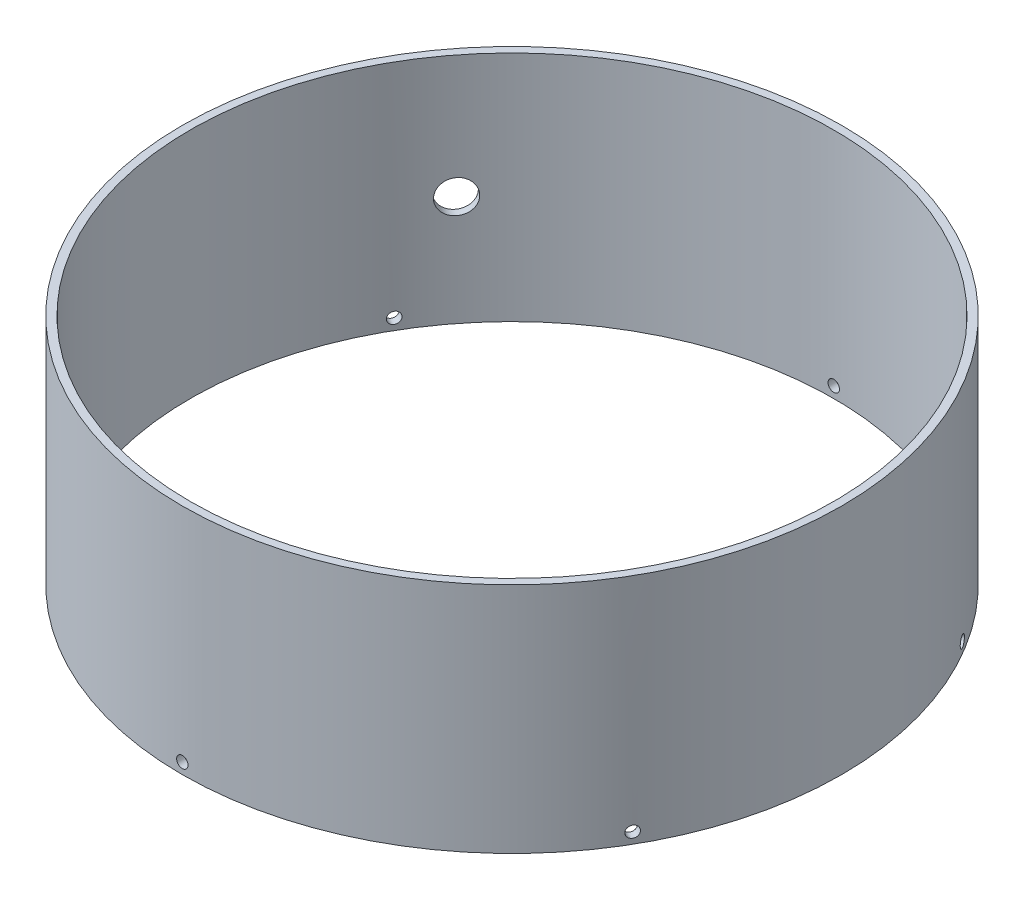
SolidWorks part; units mm, degrees
material "E-Glass Fiber"
ref_plane "Front Plane" through (0, 0, 0) normal (0, 0, 1) x (1, 0, 0)
ref_plane "Top Plane" through (0, 0, 0) normal (0, 1, 0) x (1, 0, 0)
ref_plane "Right Plane" through (0, 0, 0) normal (1, 0, 0) x (0, 0, -1)
sketch "Sketch2" plane through (0, 0, 0) normal (0, 1, 0) x (1, 0, 0)
  circle A0 centre (0, 0) radius 76.2
  circle A1 centre (0, 0) radius 74.3712
  dimension "D1" = 152.4
  dimension "D2" = 1.8288
extrude "Boss-Extrude1" add sketch "Sketch2" along normal blind 53.7718 contours A0 A1 region at (-75.9845, 0, 0)
sketch "Sketch3" plane through (0, 0, 0) normal (0, 0, 1) x (1, 0, 0)
  circle A0 centre (0, 2.54) radius 1.3208
  dimension "D1" = 2.6416
  dimension "D2" = 2.54
extrude "Cut-Extrude1" cut sketch "Sketch3" along normal up to surface (76.1886 mm away) contours A0 region at (0, 2.54, 0) up to face at (0, 53.7718, 76.2)
pattern_circular "CirPattern1" count 6 over 360 about axis through (0, 53.7718, 0) along (0, -1, 0) of "Cut-Extrude1"
sketch "Sketch4" plane through (0, 0, 0) normal (0, 1, 0) x (1, 0, 0)
  line L0 (0, 0) -> (27.9466, 0) construction
  line L1 (0, 0) -> (-34.5326, 26.9798) construction
  dimension "D1" = 142
ref_plane "Plane1" through (0, 0, 0) normal (-0.788, 0, -0.6157) x (-0.6157, 0, 0.788)
sketch "Sketch5" plane through (0, 0, 0) normal (-0.788, 0, -0.6157) x (-0.6157, 0, 0.788)
  circle A0 centre (0, 25.4) radius 3.81
  dimension "D1" = 7.62
  dimension "D2" = 25.4
extrude "Cut-Extrude2" cut sketch "Sketch5" along normal through all contours A0 region at (0, 25.4, 0)
equation "\"Middle Coupler Inner Daimeter\"= 3.875in"
equation "\"Middle Coupler  Wall Thickness\"= 0.25in"
equation "\"Middle Coupler Bottom Thickness\"= 0.2in"
equation "\"Bearing Rail Offset\"= 0.45in"
equation "\"3-56 UNF Tap\"= 0.089in"
equation "\"3-48 Tap\"= 0.079in"
equation "\"3-56 UNF Clearance\"= 0.104in"
equation "\"3-48 Clearance\"= 0.104in"
equation "\"Ball Bearing Distance\"= 0.03in"
equation "\"TCA Outer Diameter\"= 6in"
equation "\"Interstage Aeroframe Wall Thickness\"= 0.072in"
equation "\"Compression Spring OD\"= 0.42in"
equation "\"10-24 Tap\"= 0.157in"
equation "\"10-24 Clearance\"= 0.196in"
equation "\"Lower Stage Fuselage Wall Thickness\"= 0.25in"
equation "\"6-32 Tap\"= 0.107in"
equation "\"6-32 Clearance\"= 0.144"
equation "\"1/4-20 Tap\"= 0.201in"
equation "\"12-24 Tap\"= 0.177in"
equation "\"D1@Sketch2\"=\"TCA Outer Diameter\""
equation "\"D1@Sketch3\"=\"3-48 Clearance\""
equation "\"D1@Boss-Extrude1\"=2.167000in - 0.05"
